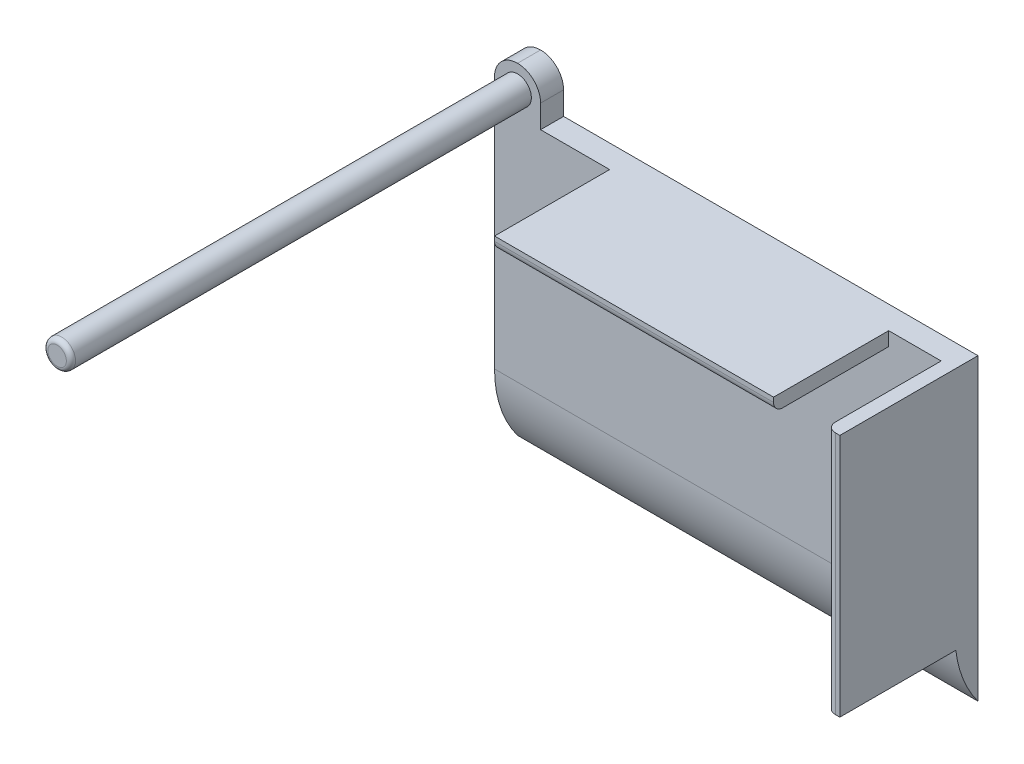
SolidWorks part; units mm, degrees
ref_plane "Front Plane" through (0, 0, 0) normal (0, 0, 1) x (1, 0, 0)
ref_plane "Top Plane" through (0, 0, 0) normal (0, 1, 0) x (1, 0, 0)
ref_plane "Right Plane" through (0, 0, 0) normal (1, 0, 0) x (0, 0, -1)
sketch "Sketch1" plane through (0, 0, 0) normal (0, 0, 1) x (1, 0, 0)
  line L1 (-50, -32.5) -> (50, -32.5)
  line L2 (-50, -32.5) -> (-50, 32.5)
  line L3 (-50, 32.5) -> (50, 32.5)
  line L4 (50, -32.5) -> (50, 32.5)
  line L5 (-50, -32.5) -> (50, 32.5) construction
  line L6 (-50, 32.5) -> (50, -32.5) construction
  point P0 (0, 0)
  dimension "D1" = 100
  dimension "D2" = 65
extrude "Boss-Extrude2" add sketch "Sketch1" along normal blind 5
ref_plane "Plane1" through (0, 0, 5) normal (0, 0, 1) x (1, 0, 0)
sketch "Sketch2" plane through (0, 0, 5) normal (0, 0, 1) x (1, 0, 0)
  line L0 (50, 32.5) -> (-50, 32.5) construction
  line L1 (-25, 32.5) -> (50, 32.5)
  line L2 (-25, 32.5) -> (-25, 29.5)
  line L3 (-25, 29.5) -> (50, 29.5)
  line L4 (50, 32.5) -> (50, 29.5)
  line L5 (50, -32.5) -> (50, 32.5) construction
  line L7 (50, 29.5) -> (47, 29.5)
  line L8 (50, 29.5) -> (50, -20.5)
  line L9 (50, -20.5) -> (47, -20.5)
  line L10 (47, 29.5) -> (47, -20.5)
  dimension "D1" = 75
  dimension "D2" = 3
  dimension "D3" = 50
  dimension "D4" = 3
ref_plane "Plane2" through (0, 32.5, 0) normal (0, 1, 0) x (1, 0, 0)
sketch "Sketch3" plane through (0, 32.5, 0) normal (0, 1, 0) x (1, 0, 0)
  line L0 (50, 0) -> (-50, 0) construction
  line L1 (-50, -5) -> (-40, -5)
  line L2 (-50, -5) -> (-50, 0)
  line L3 (-50, 0) -> (-40, 0)
  line L4 (-40, -5) -> (-40, 0)
  dimension "D1" = 10
extrude "Boss-Extrude3" add sketch "Sketch3" along normal blind 10
sketch "Sketch4" plane through (0, 0, 5) normal (0, 0, 1) x (1, 0, 0)
  line L0 (-40, 37.5) -> (-50, 37.5)
  line L1 (-40, 42.5) -> (-40, 32.5) construction
  line L2 (-50, 42.5) -> (-50, -32.5) construction
  line L3 (-45, 42.5) -> (-45, 32.82)
  line L4 (-50, 42.5) -> (-40, 42.5) construction
  line L5 (50, 32.5) -> (50, -20.5)
  line L6 (50, -20.5) -> (47, -20.5)
  line L7 (47, -20.5) -> (47, 29.5)
  line L8 (47, 29.5) -> (-25, 29.5)
  line L9 (-25, 29.5) -> (-25, 32.5)
  line L10 (-25, 32.5) -> (50, 32.5)
  circle A0 centre (-45, 37.5) radius 2
extrude "Boss-Extrude4" add sketch "Sketch4" along normal blind 25 contours L5 L6 L7 L8 L9 L10
sketch "Sketch5" plane through (0, 0, 5) normal (0, 0, 1) x (1, 0, 0)
  line L0 (-40, 37.5) -> (-50, 37.5)
  line L1 (-40, 42.5) -> (-40, 32.5) construction
  line L2 (-50, 42.5) -> (-50, -32.5) construction
  line L3 (-45, 42.5) -> (-45, 37.5)
  line L4 (-50, 42.5) -> (-40, 42.5) construction
  circle A0 centre (-45, 37.5) radius 3
  dimension "D1" = 6
extrude "Boss-Extrude5" add sketch "Sketch5" along normal blind 100 contours L0 A0 | L0 A0 L3 | A0 region at (-45, 36.2268, 5) region at (-43.7268, 38.7732, 5)
fillet "Fillet1" radius 5 2 edges at (-50, 42.5, 2.5) (-40, 42.5, 2.5)
fillet "Fillet2" radius 25 1 edges at (0, -32.5, 5)
ref_plane "Plane3" through (0, 0, 5) normal (0, 0, 1) x (1, 0, 0)
sketch "Sketch6" plane through (0, 0, 5) normal (0, 0, 1) x (1, 0, 0)
  line L0 (-40, 32.5) -> (-50, 32.5)
  line L1 (-50, 37.5) -> (-50, -17.5) construction
  dimension "D1" = 10
fillet "Fillet5" radius 1 1 edges at (-42, 37.5, 105)
ref_plane "Plane4" through (0, 0, 30) normal (0, 0, 1) x (1, 0, 0)
sketch "Sketch7" plane through (0, 0, 30) normal (0, 0, 1) x (1, 0, 0)
  line L1 (47, 29.5) -> (35.6038, 29.5)
  line L2 (47, 29.5) -> (47, 32.8746)
  line L3 (47, 32.8746) -> (35.6038, 32.8746)
  line L4 (35.6038, 29.5) -> (35.6038, 32.8746)
extrude "Cut-Extrude2" cut sketch "Sketch7" against normal blind 25
fillet "Fillet7" radius 2 2 edges at (47, 6, 30) (5.3019, 29.5, 30)
